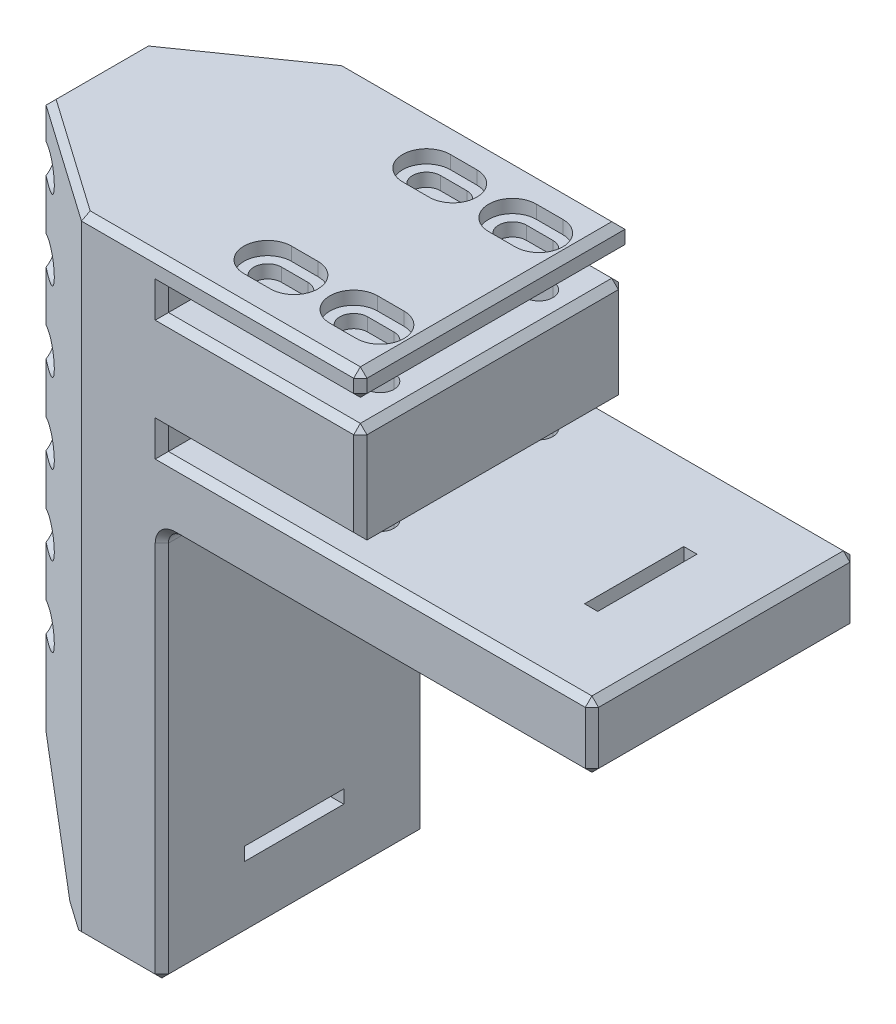
SolidWorks part; units mm, degrees
ref_plane "Front Plane" through (0, 0, 0) normal (0, 0, 1) x (1, 0, 0)
ref_plane "Top Plane" through (0, 0, 0) normal (0, 1, 0) x (1, 0, 0)
ref_plane "Right Plane" through (0, 0, 0) normal (1, 0, 0) x (0, 0, -1)
sketch "Sketch1" plane through (0, 0, 0) normal (0, 0, 1) x (1, 0, 0)
  line L0 (-15, 10.79) -> (15, 10.79)
  line L1 (-15, -7.39) -> (15, -7.39)
  line L3 (-15, 7.39) -> (15, 7.39)
  line L4 (15, -7.39) -> (15, 7.39)
  line L5 (-15, -7.39) -> (15, 7.39) construction
  line L6 (-15, 7.39) -> (15, -7.39) construction
  line L7 (15, 10.79) -> (15, 14.79)
  line L8 (15, 14.79) -> (-45, 14.79)
  line L9 (-45, 14.79) -> (-45, -80.21)
  line L10 (-45, -80.21) -> (-15, -80.21)
  line L11 (-15, -80.21) -> (-15, -22.79)
  line L12 (-13, -20.79) -> (50, -20.79)
  line L13 (50, -20.79) -> (50, -10.79)
  line L14 (50, -10.79) -> (-15, -10.79)
  line L15 (-15, -10.79) -> (-15, -7.39)
  line L16 (-15, 7.39) -> (-15, 10.79)
  arc A1 (-13, -20.79) -> (-15, -22.79) centre (-13, -22.79) ccw
  point P0 (0, 0)
  point P10 (-15, -9.09)
  point P13 (-15, 9.09)
  dimension "D6" = 2
  dimension "D7" = 65
  dimension "D1" = 4
  dimension "D2" = 3.4
  dimension "D3" = 18.18
  dimension "D4" = 30
  dimension "D5" = 30
  dimension "D8" = 10
  dimension "D9" = 95
extrude "Boss-Extrude1" add sketch "Sketch1" along normal blind 40
ref_plane "Plane1" through (0, 6.79, 0) normal (0, 1, 0) x (1, 0, 0)
sketch "Sketch2" plane through (0, 6.79, 0) normal (0, 1, 0) x (1, 0, 0)
  line L0 (-45, -20) -> (15, -20) construction
  line L1 (-45, -40) -> (-45, 0) construction
  line L2 (15, -40) -> (15, 0) construction
  circle A0 centre (-45, -20) radius 8.7
  dimension "D1" = 17.4
sketch "Sketch3" plane through (0, 14.79, 0) normal (0, 1, 0) x (1, 0, 0)
  line L0 (-43.3548, -40) -> (-45, -38.9316)
  line L1 (15, -40) -> (-45, -40) construction
  line L2 (-45, -40) -> (-45, 0) construction
  line L3 (-45, -38.9316) -> (-45, -40)
  line L4 (-45, -40) -> (-43.3548, -40)
  line L6 (-45, -20) -> (-51.6989, -20) construction
  line L7 (-45, 0) -> (-43.3548, 0)
  line L8 (-45, -1.0684) -> (-45, 0)
  line L9 (-43.3548, 0) -> (-45, -1.0684)
  dimension "D2" = 33
extrude "Cut-Extrude1" cut sketch "Sketch3" against normal blind 182
sweep "Cut-Sweep1" cut path "Sketch2" circular profile diameter 5 parameters "D3"=5
pattern_linear "LPattern1" count 6 spacing 12 along (0, -1, 0) of "Cut-Sweep1"
sketch "Sketch51" plane through (0, 14.79, 0) normal (0, 1, 0) x (1, 0, 0)
  line L0 (-27.1481, -40) -> (-45, -27.5)
  line L1 (-45, -38.9316) -> (-45, -1.0684) construction
  line L2 (-45, -27.5) -> (-45, -12.5)
  line L3 (-45, -12.5) -> (-27.1481, 0)
  line L4 (-27.1481, 0) -> (-27.1481, -45.5737)
  line L5 (15, -20) -> (-45, -20) construction
  line L6 (15, -40) -> (15, 0) construction
  line L7 (15, -40) -> (-43.3548, -40) construction
  line L8 (15, 0) -> (-43.3548, 0) construction
  line M6 (-45, -1.0684) -> (-45, -38.9316)
  line M7 (-45, -38.9316) -> (-43.3548, -40)
  line M8 (-43.3548, -40) -> (15, -40)
  line M10 (15, 0) -> (-43.3548, 0)
  line M11 (-43.3548, 0) -> (-45, -1.0684)
  dimension "D1" = 35
  dimension "D2" = 15
extrude "Cut-Extrude6" cut sketch "Sketch51" against normal blind 105 contours L3 M6 M10 M11 | L0 M8 M6 M7 region at (-39.0065, 14.79, 35.8031) region at (-39.0065, 14.79, 4.1969)
chamfer "Chamfer1" distance 1 angle 45 37 edges at (-45, 14.79, 20) (-6.0741, 14.79, 0) (17.5, -10.79, 0) (-15, -9.09, 0) (0, -7.39, 0) (15, 14.79, 20) (15, 10.79, 20) (0, 10.79, 0) (-15, 9.09, 0) (0, 7.39, 0) (15, 0, 0) (50, -15.79, 0) (50, -10.79, 20) (15, 7.39, 20) (-6.0741, 14.79, 40) (15, 12.79, 40) (0, 10.79, 40) (-15, 9.09, 40) (0, 7.39, 40) (15, 0, 40) (0, -7.39, 40) (-15, -9.09, 40) (17.5, -10.79, 40) (50, -15.79, 40) (-45, -80.21, 20) (-21.0741, -80.21, 0) (-15, -80.21, 20) (-21.0741, -80.21, 40) (-15, -51.5, 40) (18.5, -20.79, 40) (-15, -51.5, 0) (-14.4142, -21.3758, 0) (18.5, -20.79, 0) (-14.4142, -21.3758, 40) (-36.0741, 14.79, 6.25) (-36.0741, 14.79, 33.75) (50, -20.79, 20)
sketch "Sketch32" plane through (0, -7.39, 0) normal (0, -1, 0) x (1, 0, 0)
  line L0 (50, 20) -> (-15, 20) construction
  line L1 (-6, 32) -> (7, 32) construction
  line L2 (-6, 32) -> (-6, 8) construction
  line L3 (-6, 8) -> (7, 8) construction
  line L4 (7, 32) -> (7, 8) construction
  line L5 (50, 39) -> (50, 1) construction
  line L6 (-7, 32) -> (-3, 32) construction
  line L7 (15, 39) -> (15, 0) construction
  line L8 (-16, 1) -> (-16, 39) construction
  line L9 (-13, 40) -> (49, 40) construction
  line L10 (-15, 39) -> (-15, 1) construction
  line L11 (-7, 34.1) -> (-3, 34.1)
  line L12 (-7, 29.9) -> (-3, 29.9)
  line L13 (6, 32) -> (10, 32) construction
  line L14 (6, 34.1) -> (10, 34.1)
  line L15 (6, 29.9) -> (10, 29.9)
  line L16 (-7, 8) -> (-3, 8) construction
  line L19 (-7, 5.9) -> (-3, 5.9)
  line L20 (-7, 10.1) -> (-3, 10.1)
  line L21 (6, 8) -> (10, 8) construction
  line L22 (6, 5.9) -> (10, 5.9)
  line L23 (6, 10.1) -> (10, 10.1)
  circle A0 centre (7, 32) radius 2.1 construction
  circle A1 centre (-6, 32) radius 2.1 construction
  circle A2 centre (-6, 8) radius 2.1 construction
  circle A3 centre (7, 8) radius 2.1 construction
  arc A4 (-7, 34.1) -> (-7, 29.9) centre (-7, 32) ccw
  arc A5 (-3, 29.9) -> (-3, 34.1) centre (-3, 32) ccw
  arc A6 (6, 34.1) -> (6, 29.9) centre (6, 32) ccw
  arc A7 (10, 29.9) -> (10, 34.1) centre (10, 32) ccw
  arc A10 (-7, 5.9) -> (-7, 10.1) centre (-7, 8) cw
  arc A11 (-3, 10.1) -> (-3, 5.9) centre (-3, 8) cw
  arc A12 (6, 5.9) -> (6, 10.1) centre (6, 8) cw
  arc A13 (10, 10.1) -> (10, 5.9) centre (10, 8) cw
  point P10 (-6, 20)
  point P23 (-5, 32)
  point P28 (0, 0)
  point P29 (-3, 32)
  point P30 (0, 0)
  point P33 (8, 32)
  point P40 (-5, 8)
  point P47 (8, 8)
  dimension "D4" = 4.2
  dimension "D5" = 2.1
  dimension "D10" = 2.1
  dimension "D3" = 10
  dimension "D2" = 8
  dimension "D1" = 8
  dimension "D6" = 4
  dimension "D7" = 1
  dimension "D8" = 1
  dimension "D9" = 4
extrude "Cut-Extrude2" cut sketch "Sketch32" against normal blind 10 and the other way blind 90 from surface starting at face at (-0.5, 10.79, 20)
sketch "Sketch60" plane through (-15, 0, 0) normal (1, 0, 0) x (0, 0, -1)
  line L0 (-27.5, -69.21) -> (-40, -69.21) construction
  line L1 (-27.5, -68.21) -> (-12.5, -68.21)
  line L2 (-27.5, -68.21) -> (-27.5, -70.21)
  line L3 (-27.5, -70.21) -> (-12.5, -70.21)
  line L4 (-12.5, -68.21) -> (-12.5, -70.21)
  line L5 (-40, -79.21) -> (-40, -22.79) construction
  line L6 (-12.5, -69.21) -> (0, -69.21) construction
  line L7 (0, -22.79) -> (0, -79.21) construction
  line L8 (-1, -80.21) -> (-39, -80.21) construction
  dimension "D1" = 12
  dimension "D2" = 2
  dimension "D3" = 15
extrude "Cut-Extrude7" cut sketch "Sketch60" against normal blind 42
sketch "Sketch76" plane through (0, 0, 40) normal (0, 0, 1) x (1, 0, 0)
  line L0 (-45, -68.21) -> (-26.0245, -87.1855)
  line L1 (-26.0245, -87.1855) -> (-45, -87.1855)
  line L6 (-45, -68.21) -> (-45, -55.4032) construction
  line L7 (-45, -68.21) -> (-45, -87.1855)
  dimension "D1" = 45
extrude "Cut-Extrude10" cut sketch "Sketch76" against normal blind 121
sketch "Sketch77" plane through (0, -20.79, 0) normal (0, -1, 0) x (1, 0, 0)
  line L0 (23.7567, 27.5) -> (23.7567, 40) construction
  line L1 (36.3832, 27.5) -> (38.3832, 27.5)
  line L2 (36.3832, 27.5) -> (36.3832, 12.5)
  line L3 (36.3832, 12.5) -> (38.3832, 12.5)
  line L4 (38.3832, 27.5) -> (38.3832, 12.5)
  line L5 (-13, 40) -> (49, 40) construction
  line L6 (23.7567, 12.5) -> (23.7567, 0) construction
  line L7 (49, 0) -> (-13, 0) construction
  dimension "D1" = 15
  dimension "D2" = 2
extrude "Cut-Extrude11" cut sketch "Sketch77" against normal blind 121
sketch "Sketch79" plane through (0, 14.79, 0) normal (0, 1, 0) x (1, 0, 0)
  line L0 (-7, -8) -> (-3, -8) construction
  line L1 (-7, -4.4) -> (-3, -4.4)
  line L2 (-7, -11.6) -> (-3, -11.6)
  line L3 (6, -8) -> (10, -8) construction
  line L4 (6, -4.4) -> (10, -4.4)
  line L5 (6, -11.6) -> (10, -11.6)
  line L6 (-44, -20) -> (-17.0875, -20) construction
  line L7 (-44, -13.0206) -> (-44, -26.9794) construction
  line L8 (-7, -32) -> (-3, -32) construction
  line L9 (-7, -35.6) -> (-3, -35.6)
  line L10 (-7, -28.4) -> (-3, -28.4)
  line L11 (6, -32) -> (10, -32) construction
  line L12 (6, -35.6) -> (10, -35.6)
  line L13 (6, -28.4) -> (10, -28.4)
  arc A4 (-7, -4.4) -> (-7, -11.6) centre (-7, -8) ccw
  arc A5 (-3, -11.6) -> (-3, -4.4) centre (-3, -8) ccw
  arc A6 (6, -4.4) -> (6, -11.6) centre (6, -8) ccw
  arc A7 (10, -11.6) -> (10, -4.4) centre (10, -8) ccw
  arc A8 (-7, -35.6) -> (-7, -28.4) centre (-7, -32) cw
  arc A9 (-3, -28.4) -> (-3, -35.6) centre (-3, -32) cw
  arc A10 (6, -35.6) -> (6, -28.4) centre (6, -32) cw
  arc A11 (10, -28.4) -> (10, -35.6) centre (10, -32) cw
  point P3 (-5, -8)
  point P9 (8, -8)
  point P27 (-5, -32)
  point P34 (8, -32)
  dimension "D1" = 7.2
extrude "Cut-Extrude13" cut sketch "Sketch79" against normal blind 2
extrude "Cut-Extrude14" cut sketch "Sketch79<2>" along normal blind 4 from surface starting at face at (37.3832, -20.79, 20)
sketch "Sketch79<2>" plane through (0, 14.79, 0) normal (0, 1, 0) x (1, 0, 0) same geometry as "Sketch79"
equation "\"D3@Sketch32\"=10"
equation "\"D2@Sketch32\"=\"D1@Sketch32\""
